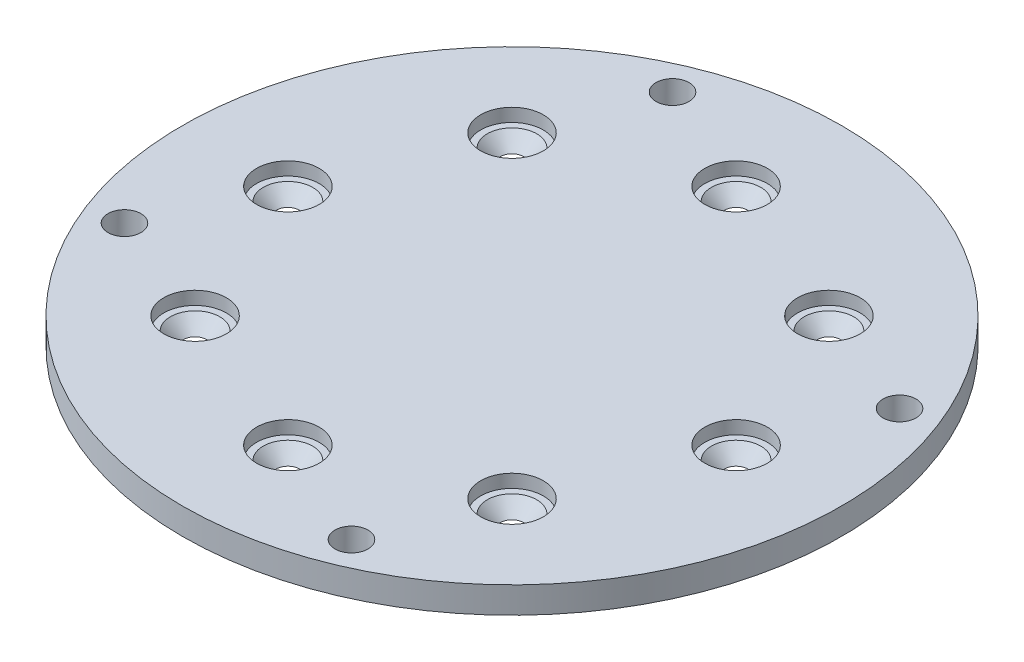
SolidWorks part; units mm, degrees
ref_plane "Front Plane" through (0, 0, 0) normal (0, 0, 1) x (1, 0, 0)
ref_plane "Top Plane" through (0, 0, 0) normal (0, 1, 0) x (1, 0, 0)
ref_plane "Right Plane" through (0, 0, 0) normal (1, 0, 0) x (0, 0, -1)
sketch "Sketch1" plane through (0, 0, 0) normal (0, 1, 0) x (1, 0, 0)
  line L1 (-50, -50) -> (50, -50)
  line L2 (-50, -50) -> (-50, 50)
  line L3 (-50, 50) -> (50, 50)
  line L4 (50, -50) -> (50, 50)
  line L5 (-50, -50) -> (50, 50) construction
  line L6 (-50, 50) -> (50, -50) construction
  point P0 (0, 0)
  dimension "D1" = 100
  dimension "D2" = 100
extrude "Boss-Extrude1" add sketch "Sketch1" along normal blind 4
sketch "Sketch2" plane through (0, 4, 0) normal (0, 1, 0) x (1, 0, 0)
  line L0 (0, 0) -> (-50, 0) construction
  line L1 (-50, 50) -> (-50, -50) construction
  line L2 (0, 0) -> (-34, 0) construction
  line L3 (0, 0) -> (-24.0416, 24.0416) construction
  circle A0 centre (-34, 0) radius 1.75
  circle A1 centre (-24.0416, 24.0416) radius 1.75
  circle A2 centre (0, 34) radius 1.75
  circle A3 centre (24.0416, 24.0416) radius 1.75
  circle A4 centre (34, 0) radius 1.75
  circle A5 centre (24.0416, -24.0416) radius 1.75
  circle A6 centre (0, -34) radius 1.75
  circle A7 centre (-24.0416, -24.0416) radius 1.75
  dimension "D1" = 3.5
  dimension "D4" = 45
  dimension "D5" = 34
  dimension "D3" = 8
extrude "Cut-Extrude1" cut sketch "Sketch2" against normal blind 10
sketch "Sketch3" plane through (0, 4, 0) normal (0, 1, 0) x (1, 0, 0)
  line L0 (-50, 50) -> (-50, -50) construction
  circle A0 centre (0, 0) radius 50
extrude "Cut-Extrude2" cut sketch "Sketch3" against normal blind 10 flip side to cut
sketch "Sketch4" plane through (0, 4, 0) normal (0, 1, 0) x (1, 0, 0)
  line L0 (-24.0416, 24.0416) -> (0, 34)
  line L1 (0, 34) -> (0, 0)
  line L2 (0, 0) -> (-19.1342, 46.194)
  circle A0 centre (0, 0) radius 50 construction
  circle A1 centre (-17.2208, 41.5746) radius 2.5
  circle A2 centre (41.5746, 17.2208) radius 2.5
  circle A3 centre (17.2208, -41.5746) radius 2.5
  circle A4 centre (-41.5746, -17.2208) radius 2.5
  point P20 (0, 0)
  dimension "D1" = 5
  dimension "D2" = 45
  dimension "D3" = 4
extrude "Cut-Extrude3" cut sketch "Sketch4" against normal blind 10 contours L2 A1 | A2 | A4 | A3 | A1 region at (-16.2405, 4, -41.9806) region at (41.5746, 4, -17.2208) region at (17.2208, 4, 41.5746) region at (-41.5746, 4, 17.2208)
sketch "Sketch5" plane through (0, 4, 0) normal (0, 1, 0) x (1, 0, 0)
  circle A0 centre (0, -34) radius 4.75
  circle A1 centre (0, -34) radius 1.75
  circle A2 centre (0, -34) radius 1.75 construction
  circle A3 centre (24.0416, -24.0416) radius 1.75
  circle A4 centre (24.0416, -24.0416) radius 1.75 construction
  circle A5 centre (34, 0) radius 1.75
  circle A6 centre (34, 0) radius 1.75 construction
  circle A7 centre (24.0416, 24.0416) radius 1.75
  circle A8 centre (24.0416, 24.0416) radius 1.75 construction
  circle A9 centre (-24.0416, -24.0416) radius 1.75
  circle A10 centre (-24.0416, -24.0416) radius 1.75 construction
  circle A11 centre (-34, 0) radius 1.75
  circle A12 centre (-34, 0) radius 1.75 construction
  circle A13 centre (-24.0416, 24.0416) radius 1.75
  circle A14 centre (-24.0416, 24.0416) radius 1.75 construction
  circle A15 centre (0, 34) radius 1.75
  circle A16 centre (0, 34) radius 1.75 construction
  circle A17 centre (24.0416, -24.0416) radius 4.75
  circle A18 centre (34, 0) radius 4.75
  circle A19 centre (24.0416, 24.0416) radius 4.75
  circle A20 centre (-24.0416, -24.0416) radius 4.75
  circle A21 centre (-34, 0) radius 4.75
  circle A22 centre (-24.0416, 24.0416) radius 4.75
  circle A23 centre (0, 34) radius 4.75
  dimension "D1" = 0
  dimension "D2" = 0
  dimension "D3" = 0
  dimension "D4" = 0
  dimension "D5" = 0
  dimension "D6" = 0
  dimension "D7" = 0
  dimension "D8" = 0
  dimension "D9" = 3
extrude "Cut-Extrude4" cut sketch "Sketch5" against normal blind 2
chamfer "Chamfer1" distance 2 angle 45 8 edges at (0, 2, -32.25) (24.0416, 2, -22.2916) (34, 2, 1.75) (24.0416, 2, 25.7916) (0, 2, 35.75) (-24.0416, 2, 25.7916) (-24.0416, 2, -22.2916) (-34, 2, 1.75)
